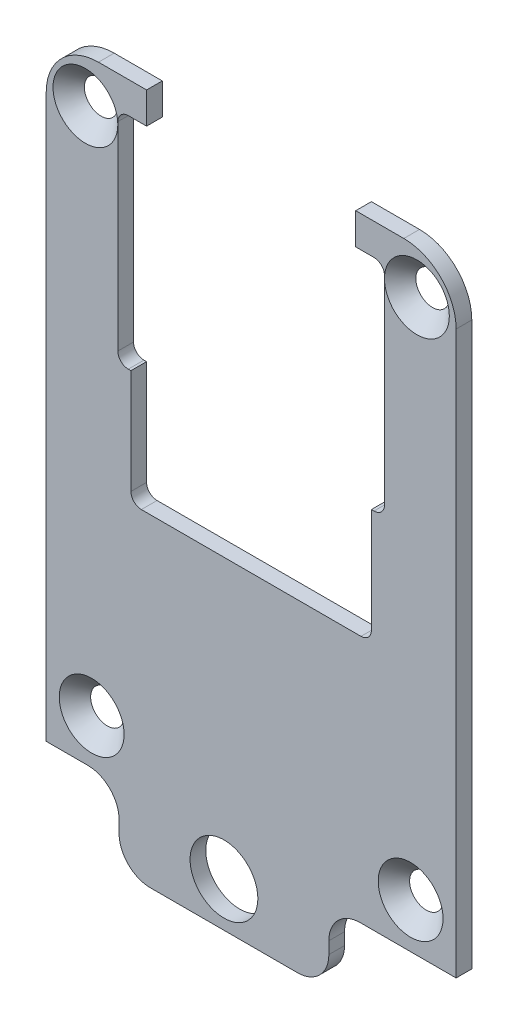
SolidWorks part; units mm, degrees
ref_plane "Front Plane" through (0, 0, 0) normal (0, 0, 1) x (1, 0, 0)
ref_plane "Top Plane" through (0, 0, 0) normal (0, 1, 0) x (1, 0, 0)
ref_plane "Right Plane" through (0, 0, 0) normal (1, 0, 0) x (0, 0, -1)
sketch "Sketch1" plane through (0, 0, 0) normal (0, 0, 1) x (1, 0, 0)
  line L0 (39.2227, 24.6544) -> (39.2227, -29.0919) construction
  line L1 (0.0227, -29.0919) -> (39.2227, -29.0919)
  line L2 (0.0227, -29.0919) -> (0.0227, 29.6544)
  line L3 (0.0227, 29.6544) -> (39.2227, 29.6544)
  line L4 (39.2227, -29.0919) -> (39.2227, 29.6544)
  line L5 (0.0227, -29.0919) -> (39.2227, 29.6544) construction
  line L6 (0.0227, 29.6544) -> (39.2227, -29.0919) construction
  line L7 (0.0227, 24.6544) -> (0.0227, -29.0919) construction
  line L8 (25.6527, -29.0919) -> (39.2227, -29.0919) construction
  line L15 (5.0227, 29.6544) -> (8.1227, 29.6544) construction
  point P4 (19.6227, 0.2812)
extrude "Base" add sketch "Sketch1" along normal blind 1.5 contours L2 L3 L4 L1
sketch "Sketch2" plane through (0, 0, 1.5) normal (0, 0, 1) x (1, 0, 0)
  line L0 (0.0227, 29.6544) -> (39.2227, 29.6544) construction
  line L1 (8.1227, 29.6544) -> (31.1227, 29.6544)
  line L2 (8.1227, 29.6544) -> (8.1227, 2.6544)
  line L3 (8.1227, 2.6544) -> (31.1227, 2.6544)
  line L4 (31.1227, 29.6544) -> (31.1227, 2.6544)
  line L5 (8.1227, 29.6544) -> (31.1227, 2.6544) construction
  line L6 (8.1227, 2.6544) -> (31.1227, 29.6544) construction
  line L7 (8.1227, 46.7053) -> (8.1227, 21.3403) construction
  line L8 (6.8727, 26.6544) -> (32.3727, 26.6544)
  line L9 (6.8727, 26.6544) -> (6.8727, 5.6544)
  line L10 (6.8727, 5.6544) -> (32.3727, 5.6544)
  line L11 (32.3727, 26.6544) -> (32.3727, 5.6544)
  line L12 (6.8727, 26.6544) -> (32.3727, 5.6544) construction
  line L13 (6.8727, 5.6544) -> (32.3727, 26.6544) construction
  line L14 (8.1227, 2.6544) -> (31.1227, 2.6544)
  line L15 (8.1227, 2.6544) -> (8.1227, -5.3456)
  line L16 (8.1227, -5.3456) -> (31.1227, -5.3456)
  line L17 (31.1227, 2.6544) -> (31.1227, -5.3456)
  line L18 (8.1227, 2.6544) -> (31.1227, -5.3456) construction
  line L19 (8.1227, -5.3456) -> (31.1227, 2.6544) construction
  line L20 (31.1227, 21.3403) -> (31.1227, 46.7053) construction
  line L22 (0.0227, 29.6544) -> (39.2227, 29.6544) construction
  point P4 (19.6227, 16.1544)
  point P7 (0, 0)
  point P9 (8.1602, 29.6544)
  point P11 (8.1227, 29.6544)
  point P16 (19.6227, 16.1544)
  point P17 (19.6227, -1.3456)
  point P20 (31.1227, 29.6544)
  line M8 (39.2227, 29.6544) -> (0.0227, 29.6544)
  dimension "D1" = 27
  dimension "D2" = 25.5
  dimension "D3" = 21
  dimension "D5" = 8
sketch "Sketch11" [suppressed] plane through (0, 0, 0) normal (0, 0, 1) x (1, 0, 0)
  line L0 (0.0227, -29.0919) -> (39.2227, -29.0919) construction
  line L1 (5.0927, -31.6169) -> (23.1528, -31.6169)
  line L2 (5.0927, -31.6169) -> (5.0927, -29.0919)
  line L3 (5.0927, -29.0919) -> (23.1528, -29.0919)
  line L4 (23.1528, -31.6169) -> (23.1528, -29.0919)
  line L5 (5.0927, -31.6169) -> (23.1528, -29.0919) construction
  line L6 (5.0927, -29.0919) -> (23.1528, -31.6169) construction
  arc A0 (25.6527, -29.0919) -> (23.1527, -31.5919) centre (25.6527, -31.5919) ccw construction
  point P4 (14.1228, -30.3544)
extrude "Antenna connector cover" [suppressed] add sketch "Sketch11" along normal up to surface (1.5 mm away) up to face at (19.6227, 0.2812, 1.5)
fillet "Antenna connector fillet" [suppressed] radius 2.5
fillet "Front fillet" radius 5 2 edges at (0.0227, 29.6544, 0.75) (39.2227, 29.6544, 0.75)
sketch "Sketch4" plane through (0, 0, 1.5) normal (0, 0, 1) x (1, 0, 0)
  line L0 (0.0227, -9.5456) -> (39.2227, -9.5456) construction
  line L3 (19.6227, 29.6544) -> (19.6227, -34.1456) construction
  circle A1 centre (3.7727, 25.4083) radius 1.6 construction
  circle A4 centre (34.8727, -24.7956) radius 1.6
  circle A5 centre (4.3727, -24.7956) radius 1.6
  circle A6 centre (3.7727, 25.4083) radius 1.6
  circle A7 centre (35.4727, 25.4083) radius 1.6
  circle A8 centre (35.4727, 25.4083) radius 1.6 construction
extrude "Bolt hole cut" cut sketch "Sketch4" against normal up to next
chamfer "Bolt head chamber" distance 1.5 angle 45 4 edges at (37.0727, 25.4083, 1.5) (33.2727, -24.7956, 1.5) (5.9727, -24.7956, 1.5) (5.3727, 25.4083, 1.5)
extrude "Camra hole" cut sketch "Sketch2" against normal up to next contours L2 L10 L4 L8 | L9 L10 L2 L8 | L11 L8 L4 L10 | L10 L2 L3 L4 | L17 L3 L15 L16 | L2 L8 L4 M8 region at (19.6227, 28.1544, 1.5) region at (19.6227, 16.1544, 1.5) region at (7.4977, 16.1544, 1.5) region at (31.7477, 16.1544, 1.5) region at (19.6227, 4.1544, 1.5) region at (19.6227, -1.3456, 1.5)
sketch "Sketch10" plane through (0, 0, 1.5) normal (0, 0, 1) x (1, 0, 0)
  line L0 (9.8727, -15.0956) -> (29.3727, -15.0956) construction
  line L1 (9.8727, -13.3456) -> (29.3727, -13.3456)
  line L2 (9.8727, -16.8456) -> (29.3727, -16.8456)
  line L3 (8.1227, -5.3456) -> (31.1227, -5.3456) construction
  line L5 (8.1227, 5.6544) -> (8.1227, -5.3456) construction
  line L6 (31.1227, 5.6544) -> (31.1227, -5.3456) construction
  arc A0 (9.8727, -13.3456) -> (9.8727, -16.8456) centre (9.8727, -15.0956) ccw
  arc A1 (29.3727, -16.8456) -> (29.3727, -13.3456) centre (29.3727, -15.0956) ccw
  point P2 (19.6227, -15.0956)
  dimension "D1" = 3.5
  dimension "D2" = 8
extrude "GoPro strap holder" [suppressed] cut sketch "Sketch10" against normal up to next
sketch "Sketch9" plane through (0, 0, 1.5) normal (0, 0, 1) x (1, 0, 0)
  line L0 (9.6227, 21.3403) -> (9.6227, 46.7053) construction
  line L1 (8.1227, 29.6544) -> (9.6227, 29.6544)
  line L2 (8.1227, 29.6544) -> (8.1227, 26.6544)
  line L3 (8.1227, 26.6544) -> (9.6227, 26.6544)
  line L4 (9.6227, 29.6544) -> (9.6227, 26.6544)
  line L5 (8.1227, 29.6544) -> (9.6227, 26.6544) construction
  line L6 (8.1227, 26.6544) -> (9.6227, 29.6544) construction
  line L7 (7.6217, -36.2417) -> (31.6237, -36.2417) construction
  line L8 (19.6227, -36.2417) -> (19.6227, 29.6544) construction
  line L9 (8.1227, 28.1583) -> (8.1227, 29.7583) construction
  line L10 (6.8727, 26.6544) -> (8.1227, 26.6544) construction
  line L11 (31.1227, 26.6544) -> (29.6227, 29.6544) construction
  line L12 (31.1227, 29.6544) -> (29.6227, 26.6544) construction
  line L13 (29.6227, 29.6544) -> (29.6227, 26.6544)
  line L14 (31.1227, 26.6544) -> (29.6227, 26.6544)
  line L15 (31.1227, 29.6544) -> (31.1227, 26.6544)
  line L16 (31.1227, 29.6544) -> (29.6227, 29.6544)
  line L17 (34.2227, 29.6544) -> (5.0227, 29.6544) construction
  line L18 (5.0227, 29.6544) -> (8.1227, 29.6544) construction
  point P4 (8.8727, 28.1544)
  point P21 (30.3727, 28.1544)
  line M10 (8.1227, 29.6544) -> (5.0227, 29.6544)
extrude "Camera side mount holder" add sketch "Sketch9" against normal up to surface (1.5 mm away) contours L4 L2 L3 M10 | L15 L13 L14 M10 region at (8.8727, 28.1544, 1.5) region at (30.3727, 28.1544, 1.5) up to face at (5.9727, -24.7956, 0)
fillet "Fillet1" radius 1 2 edges at (32.3727, 5.6544, 0.75) (6.8727, 5.6544, 0.75)
sketch "Sketch12" plane through (0, 0, 0) normal (0, 0, -1) x (-1, 0, 0)
  line L0 (-0.0227, -29.0919) -> (-39.2227, -29.0919) construction
  line L1 (-6.9927, -29.0919) -> (-27.0527, -29.0919)
  line L2 (-6.9927, -29.0919) -> (-6.9927, -36.2417)
  line L3 (-6.9927, -36.2417) -> (-27.0527, -36.2417)
  line L4 (-27.0527, -29.0919) -> (-27.0527, -36.2417)
  line L5 (-6.9927, -29.0919) -> (-27.0527, -36.2417) construction
  line L6 (-6.9927, -36.2417) -> (-27.0527, -29.0919) construction
  line L7 (-36.1375, -36.2417) -> (-24.0527, -36.2417) construction
  line L8 (-27.0527, -33.2417) -> (-27.0527, -32.0919) construction
  line L9 (-6.9927, -33.2417) -> (-6.9927, -32.0919) construction
  point P4 (-17.0227, -32.6668)
extrude "Antenna connector top base" add sketch "Sketch12" against normal up to surface (1.5 mm away) up to face at (37.9727, -24.7956, 1.5)
sketch "Sketch13" plane through (0, 0, 1.5) normal (0, 0, 1) x (1, 0, 0)
  circle A2 centre (17.0227, -31.9919) radius 3.24
  circle A3 centre (17.0227, -31.9919) radius 3.24
  dimension "D1" = 0.6
extrude "Antenna connector top cut" cut sketch "Sketch13" against normal up to next
fillet "Antenna top connector fillet" radius 3 4 edges at (6.9927, -29.0919, 0.75) (6.9927, -36.2417, 0.75) (27.0527, -36.2417, 0.75) (27.0527, -29.0919, 0.75)
fillet "Fillet2" radius 1 4 edges at (8.1227, -5.3456, 0.75) (31.1227, -5.3456, 0.75) (32.3727, 26.6544, 0.75) (6.8727, 26.6544, 0.75)
